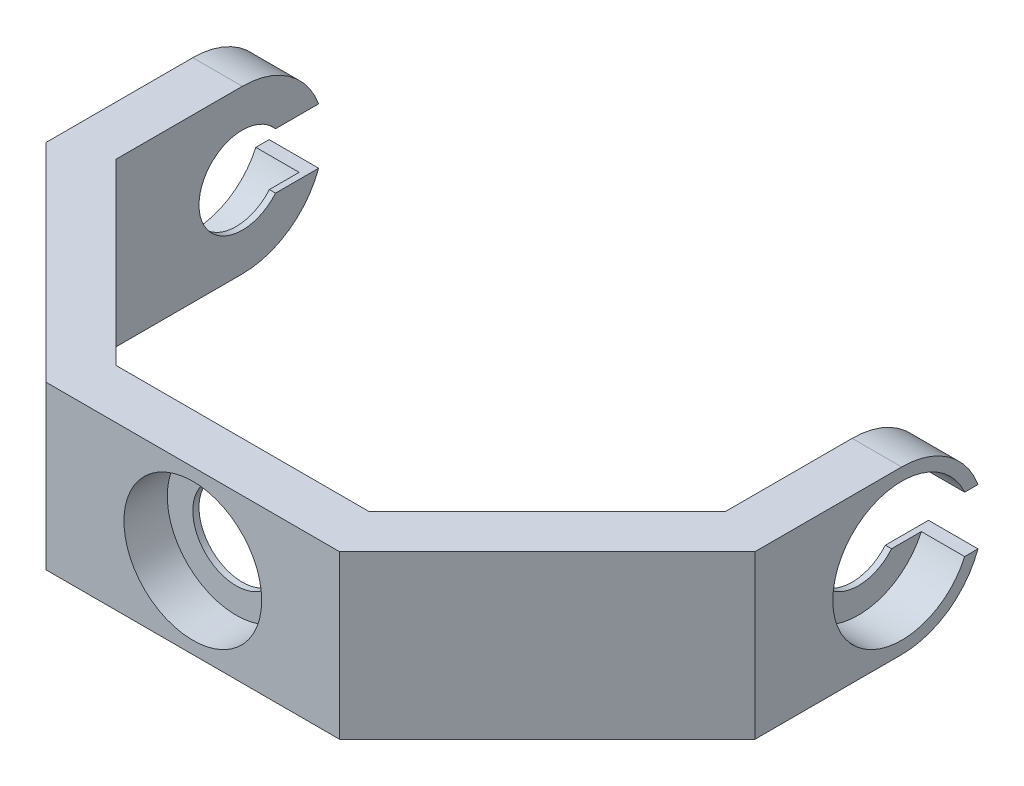
SolidWorks part; units mm, degrees
ref_plane "Front Plane" through (0, 0, 0) normal (0, 0, 1) x (1, 0, 0)
ref_plane "Top Plane" through (0, 0, 0) normal (0, 1, 0) x (1, 0, 0)
ref_plane "Right Plane" through (0, 0, 0) normal (1, 0, 0) x (0, 0, -1)
sketch "Sketch1" plane through (0, 0, 0) normal (0, 1, 0) x (1, 0, 0)
  line L0 (49.25, 0) -> (-49.25, 0) construction
  line L1 (-49.25, 13.125) -> (-49.25, -13.125)
  line L2 (-49.25, 13.125) -> (-57.25, 13.125)
  line L3 (-57.25, 13.125) -> (-57.25, -23.7137)
  line L4 (0, -1000) -> (0, 49000) construction
  line L5 (-23.7137, -57.25) -> (23.7137, -57.25)
  line L6 (-49.25, -13.125) -> (-49.25, -20.4)
  line L7 (-20.4, -49.25) -> (20.4, -49.25)
  line L12 (-47.4592, 11.125) -> (-47.4592, -11.125) construction
  line L13 (-49.25, -20.4) -> (-20.4, -49.25)
  line L14 (-57.25, -23.7137) -> (-23.7137, -57.25)
  line L15 (49.25, -20.4) -> (20.4, -49.25)
  line L16 (57.25, -23.7137) -> (23.7137, -57.25)
  line L17 (49.25, -13.125) -> (49.25, -20.4)
  line L18 (49.25, 13.125) -> (49.25, -13.125)
  line L19 (49.25, 13.125) -> (57.25, 13.125)
  line L20 (57.25, 13.125) -> (57.25, -23.7137)
  line L21 (-78.0047, 2.6978) -> (-12.1815, -63.1254) construction
  circle A0 centre (0, 0) radius 44.45 construction
  point P6 (0, 0)
  point P9 (-49.25, 0)
  point P14 (0, -49.25)
  point P16 (0, -57.25)
  point P17 (0, -57.25)
  point P18 (0, -49.25)
  point P24 (-47.4592, 0)
  dimension "D1" = 88.9
  dimension "D2" = 98.5
  dimension "D3" = 2
  dimension "D4" = 8
  dimension "D5" = 8
  dimension "D6" = 49.25
  dimension "D7" = 22.25
  dimension "D8" = 45
  dimension "D9" = 49.25
  dimension "D10" = 8
  dimension "D11" = 4
extrude "Boss-Extrude1" add sketch "Sketch1" along normal mid plane 26.25
sketch "Sketch2" plane through (-57.25, 0, 0) normal (-1, 0, 0) x (0, 0, 1)
  line L0 (-13.125, 13.125) -> (23.7137, 13.125) construction
  line L2 (-13.125, 13.125) -> (-13.125, -13.125) construction
  line L3 (-13.125, -13.125) -> (23.7137, -13.125) construction
  line L4 (0, 0) -> (-13.125, 0) construction
  line L5 (-5.3619, 4.5) -> (-12.3295, 4.5)
  line L6 (-5.3619, -4.5) -> (-12.3295, -4.5)
  circle A0 centre (0, 0) radius 13.125
  circle A1 centre (0, 0) radius 11.125
  circle A2 centre (0, 0) radius 7
  line M1 (-13.125, -13.125) -> (23.7137, -13.125)
  line M3 (23.7137, 13.125) -> (-13.125, 13.125)
  line M4 (-13.125, 13.125) -> (-13.125, -13.125)
  dimension "D1" = 2
  dimension "D2" = 14
  dimension "D3" = 9
extrude "Cut-Extrude1" cut sketch "Sketch2" against normal up to surface (106.5 mm away) contours A0 M3 M4 | A0 M4 M1 | A2 | A2 L4 A1 L6 | L4 A2 L5 A1 | A1 L4 A0 L6 | L4 A1 L5 A0 region at (-57.25, -2.3062, -8.6308) region at (-57.25, 2.3062, -8.6308) region at (-57.25, 2.3267, -6.3917) region at (-57.25, -2.2777, -11.8327) region at (-57.25, 2.2777, -11.8327) region at (-57.25, 10.1933, -10.1933) region at (-57.25, -10.1933, -10.1933)
extrude "Cut-Extrude2" cut sketch "Sketch2<4>" against normal blind 7 contours A1 A2 region at (-57.25, 4.808, -7.7681)
sketch "Sketch2<4>" plane through (-57.25, 0, 0) normal (-1, 0, 0) x (0, 0, 1) same geometry as "Sketch2"
mirror "Mirror1" about plane through (0, 0, 0) normal (1, 0, 0) of "Cut-Extrude2", "Cut-Extrude1"
ref_axis "Axis1" through (0, 14.4375, 0) along (0, -1, 0)
sketch "Sketch3" plane through (0, 0, 57.25) normal (0, 0, 1) x (1, 0, 0)
  circle A0 centre (0, 0) radius 11.125
  dimension "D1" = 22.25
extrude "Cut-Extrude3" cut sketch "Sketch3" against normal blind 7
sketch "Sketch4" plane through (0, 0, 50.25) normal (0, 0, 1) x (1, 0, 0)
  circle A0 centre (0, 0) radius 7
  dimension "D1" = 14
extrude "Cut-Extrude4" cut sketch "Sketch4" against normal up to next
sketch "GearMockup" plane through (0, 13.125, 0) normal (0, 1, 0) x (1, 0, 0)
  line L0 (-79.2669, -6.7781) -> (-6.7781, -79.2669) construction
  line L1 (-1000, 0) -> (49000, 0) construction
  line L2 (0, 0) -> (0, -89.6259) construction
  line L3 (-57.25, -23.7137) -> (-23.7137, -57.25) construction
  line L4 (-4.4796, -76.9684) -> (-9.0766, -81.5654)
  line L5 (-76.9684, -4.4796) -> (-81.5654, -9.0766)
  line L6 (-4.4796, -76.9684) -> (4.4796, -76.9684)
  line L7 (-76.9684, 4.4796) -> (-76.9684, -4.4796)
  line L8 (18.3668, -69.086) -> (69.086, -18.3668) construction
  line L9 (23.7137, -57.25) -> (57.25, -23.7137) construction
  line L10 (66.7875, -16.0683) -> (71.3845, -20.6653)
  line L11 (16.0683, -66.7875) -> (20.6653, -71.3845)
  line L12 (-16.0683, -66.7875) -> (16.0683, -66.7875)
  line L13 (66.7875, 16.0683) -> (66.7875, -16.0683)
  line L14 (-35.2443, -35.2443) -> (-50.8007, -50.8007)
  point P15 (-6.7781, -79.2669)
  point P16 (-79.2669, -6.7781)
  point P19 (0, -76.9684)
  point P22 (-76.9684, 0)
  point P27 (69.086, -18.3668)
  point P30 (18.3668, -69.086)
  point P33 (0, -66.7875)
  point P36 (66.7875, 0)
  point P40 (-43.0225, -43.0225)
  dimension "D1" = 22
sketch "BeltMockup" plane through (0, 13.125, 0) normal (0, 1, 0) x (1, 0, 0)
  line L0 (0, 0) -> (0, -111.6595) construction
  line L1 (86.9579, 0) -> (-86.9579, 0) construction
  point P6 (0, 0)
